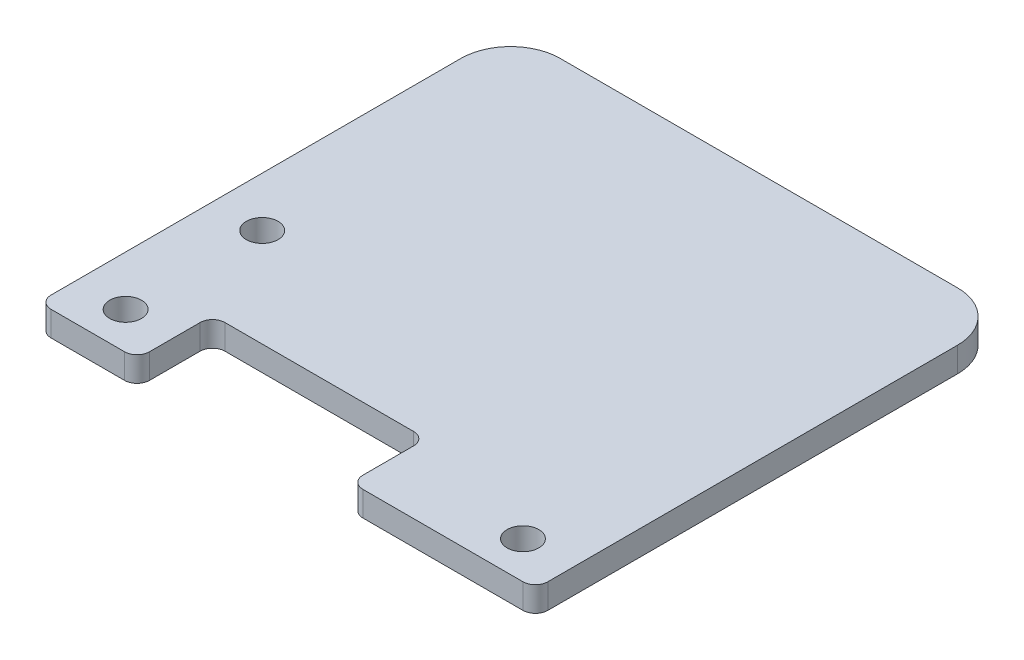
SolidWorks part; units mm, degrees
ref_plane "Front Plane" through (0, 0, 0) normal (0, 0, 1) x (1, 0, 0)
ref_plane "Top Plane" through (0, 0, 0) normal (0, 1, 0) x (1, 0, 0)
ref_plane "Right Plane" through (0, 0, 0) normal (1, 0, 0) x (0, 0, -1)
sketch "Sketch1" plane through (0, 0, 0) normal (0, 1, 0) x (1, 0, 0)
  line L1 (-31.75, 30.1625) -> (31.75, 30.1625)
  line L2 (-31.75, 30.1625) -> (-31.75, -30.1625)
  line L3 (-31.75, -30.1625) -> (31.75, -30.1625)
  line L4 (31.75, 30.1625) -> (31.75, -30.1625)
  line L5 (-31.75, 30.1625) -> (31.75, -30.1625) construction
  line L6 (-31.75, -30.1625) -> (31.75, 30.1625) construction
  point P0 (0, 0)
  dimension "D1" = 63.5
  dimension "D2" = 60.325
extrude "Boss-Extrude1" add sketch "Sketch1" along normal blind 3.175
sketch "Sketch2" plane through (0, 0, 0) normal (0, -1, 0) x (-1, 0, 0)
  line L0 (31.75, -30.1625) -> (-31.75, -30.1625) construction
  line L1 (-25.4, -25.4) -> (-31.75, -25.4) construction
  line L2 (-31.75, -30.1625) -> (-31.75, 30.1625) construction
  line L3 (25.4, -25.4) -> (31.75, -25.4) construction
  line L4 (31.75, 30.1625) -> (31.75, -30.1625) construction
  circle A0 centre (-25.4, -25.4) radius 2.032
  circle A1 centre (25.4, -25.4) radius 2.032
  dimension "D2" = 4.064
  dimension "D1" = 4.7625
  dimension "D3" = 50.8
extrude "Cut-Extrude1" cut sketch "Sketch2" against normal through all
sketch "Sketch3" plane through (0, 3.175, 0) normal (0, 1, 0) x (1, 0, 0)
  line L0 (-31.75, -30.1625) -> (31.75, -30.1625) construction
  line L1 (-19.177, -30.1625) -> (8.128, -30.1625)
  line L2 (-19.177, -30.1625) -> (-19.177, -20.5105)
  line L3 (-19.177, -20.5105) -> (8.128, -20.5105)
  line L4 (8.128, -30.1625) -> (8.128, -20.5105)
  line L5 (-31.75, 30.1625) -> (-31.75, -30.1625) construction
  dimension "D1" = 12.573
  dimension "D2" = 27.305
  dimension "D3" = 9.652
extrude "Cut-Extrude2" cut sketch "Sketch3" against normal through all
fillet "Fillet1" radius 1.5875 6 edges at (-31.75, 1.5875, 30.1625) (-19.177, 1.5875, 30.1625) (-19.177, 1.5875, 20.5105) (8.128, 1.5875, 20.5105) (8.128, 1.5875, 30.1625) (31.75, 1.5875, 30.1625)
fillet "Fillet2" radius 6.35 2 edges at (-31.75, 1.5875, -30.1625) (31.75, 1.5875, -30.1625)
sketch "Sketch4" plane through (0, 3.175, 0) normal (0, 1, 0) x (1, 0, 0)
  circle A0 centre (-25.4, -7.9375) radius 2.032 construction
  circle A1 centre (-25.4, -7.9375) radius 2.032
extrude "Cut-Extrude3" cut sketch "Sketch4" against normal through all
